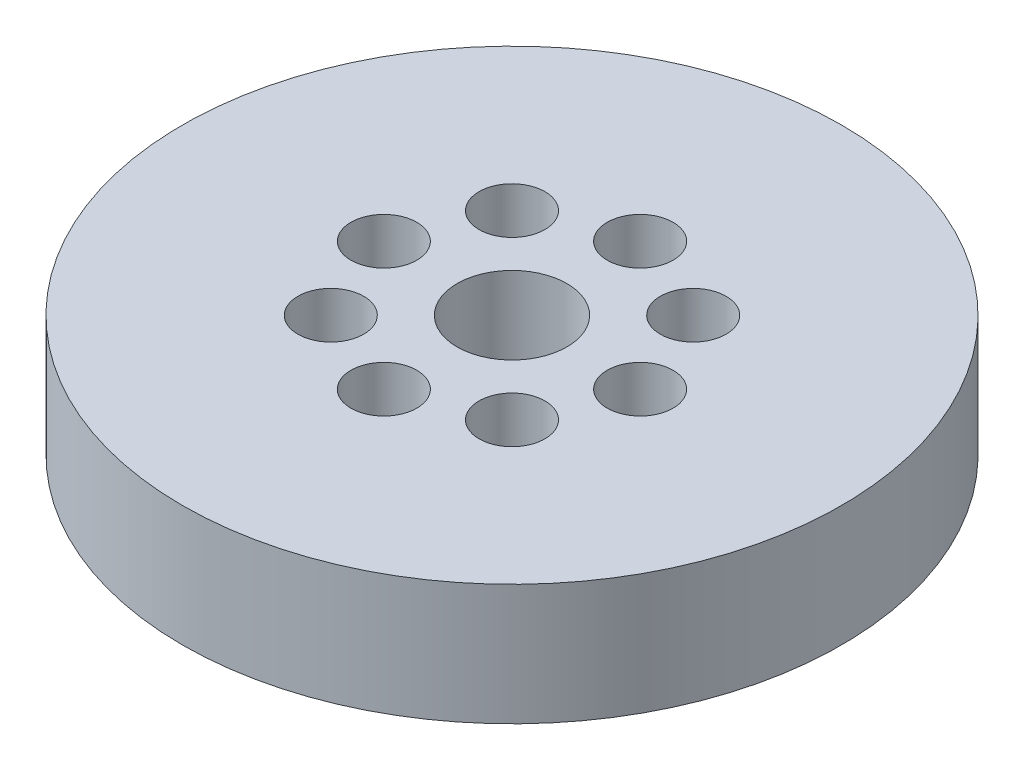
SolidWorks part; units mm, degrees
ref_plane "Front Plane" through (0, 0, 0) normal (0, 0, 1) x (1, 0, 0)
ref_plane "Top Plane" through (0, 0, 0) normal (0, 1, 0) x (1, 0, 0)
ref_plane "Right Plane" through (0, 0, 0) normal (1, 0, 0) x (0, 0, -1)
sketch "Sketch1" plane through (0, 0, 0) normal (0, 1, 0) x (1, 0, 0)
  circle A0 centre (0, 0) radius 30
  dimension "FLANGE_OD" = 60
extrude "Boss-Extrude1" add sketch "Sketch1" along normal blind 11
sketch "Sketch2" plane through (0, 0, 0) normal (0, 1, 0) x (1, 0, 0)
  circle A0 centre (0, 0) radius 5
  dimension "BORE_D" = 10
extrude "Cut-Extrude1" cut sketch "Sketch2" along normal through all
sketch "Sketch3" plane through (0, 11, 0) normal (0, 1, 0) x (1, 0, 0)
  circle A0 centre (0, 0) radius 11.6646 construction
  circle A1 centre (-11.6646, 0) radius 2.9964
  dimension "BOLT_D" = 5.9928
  dimension "BOLT_PCD" = 23.3292
extrude "Cut-Extrude2" cut sketch "Sketch3" against normal blind 8.2541
pattern_circular "CirPattern1" count 8 over 360 about axis through (0, 0, 0) along (0, 1, 0) of "Cut-Extrude2"
